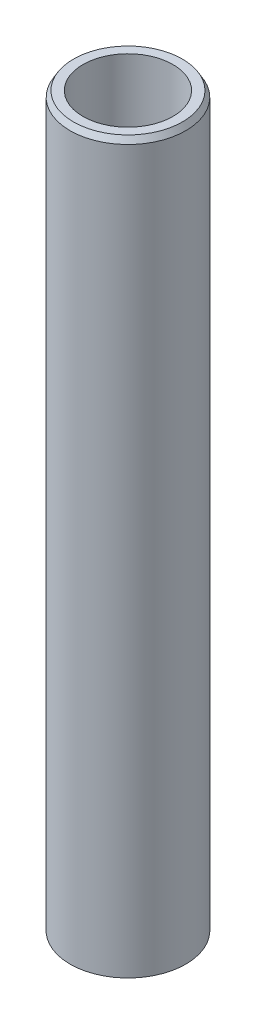
SolidWorks part; units mm, degrees
ref_plane "Front Plane" through (0, 0, 0) normal (0, 0, 1) x (1, 0, 0)
ref_plane "Top Plane" through (0, 0, 0) normal (0, 1, 0) x (1, 0, 0)
ref_plane "Right Plane" through (0, 0, 0) normal (1, 0, 0) x (0, 0, -1)
sketch "Sketch1" plane through (0, 0, 0) normal (0, 1, 0) x (1, 0, 0)
  circle A0 centre (0, 0) radius 47.5
  dimension "SHAFT_OD" = 95
extrude "Boss-Extrude1" add sketch "Sketch1" along normal blind 600
sketch "Sketch2" plane through (0, 0, 0) normal (0, 1, 0) x (1, 0, 0)
  circle A0 centre (0, 0) radius 36.9378
  dimension "BORE_D" = 73.8756
extrude "Cut-Extrude1" cut sketch "Sketch2" along normal through all
chamfer "Chamfer1" distance 4.8297 angle 30 2 edges at (0, 600, 47.5) (0, 0, 47.5) first distance on face at (0, 600, 47.5) first distance on face at (0, 0, 36.9378)
